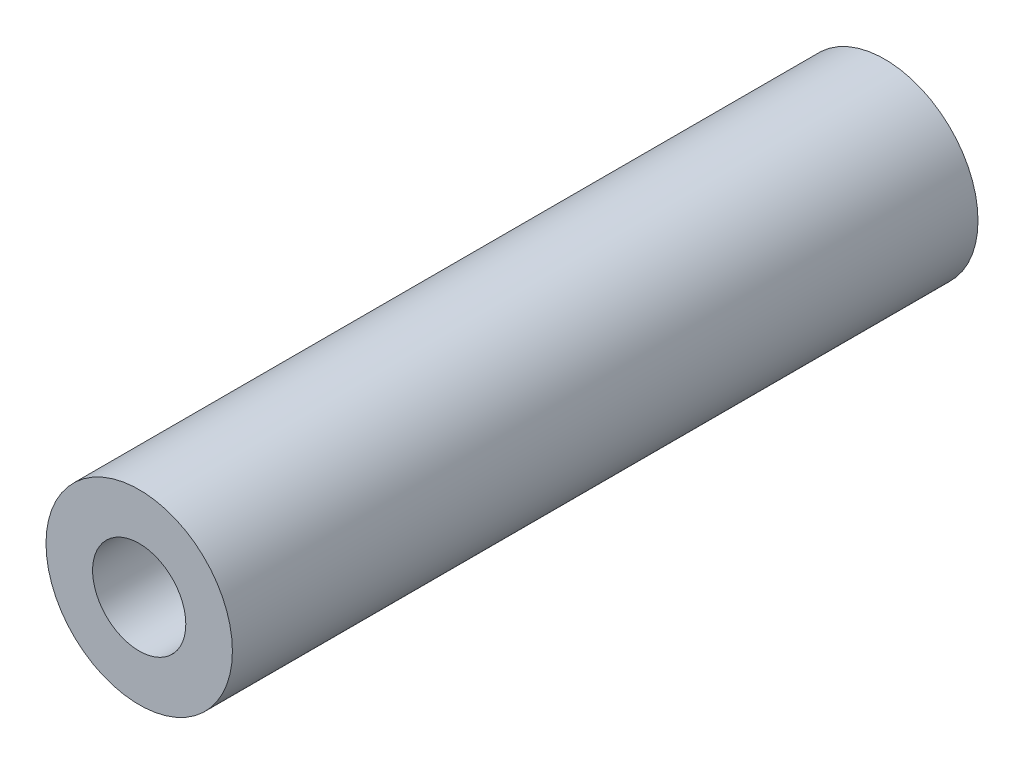
SolidWorks part; units mm, degrees
material "Nylon 101"
ref_plane "Front Plane" through (0, 0, 0) normal (0, 0, 1) x (1, 0, 0)
ref_plane "Top Plane" through (0, 0, 0) normal (0, 1, 0) x (1, 0, 0)
ref_plane "Right Plane" through (0, 0, 0) normal (1, 0, 0) x (0, 0, -1)
sketch "Sketch1" plane through (0, 0, 0) normal (0, 0, 1) x (1, 0, 0)
  circle A0 centre (0, 0) radius 3.175
  dimension "D1" = 6.35
extrude "Boss-Extrude1" add sketch "Sketch1" along normal blind 12.7 and the other way blind 12.7
sketch "Sketch2" plane through (0, 0, 12.7) normal (0, 0, 1) x (1, 0, 0)
  circle A0 centre (0, 0) radius 1.5875
  dimension "D1" = 3.175
extrude "Cut-Extrude1" cut sketch "Sketch2" against normal through all
